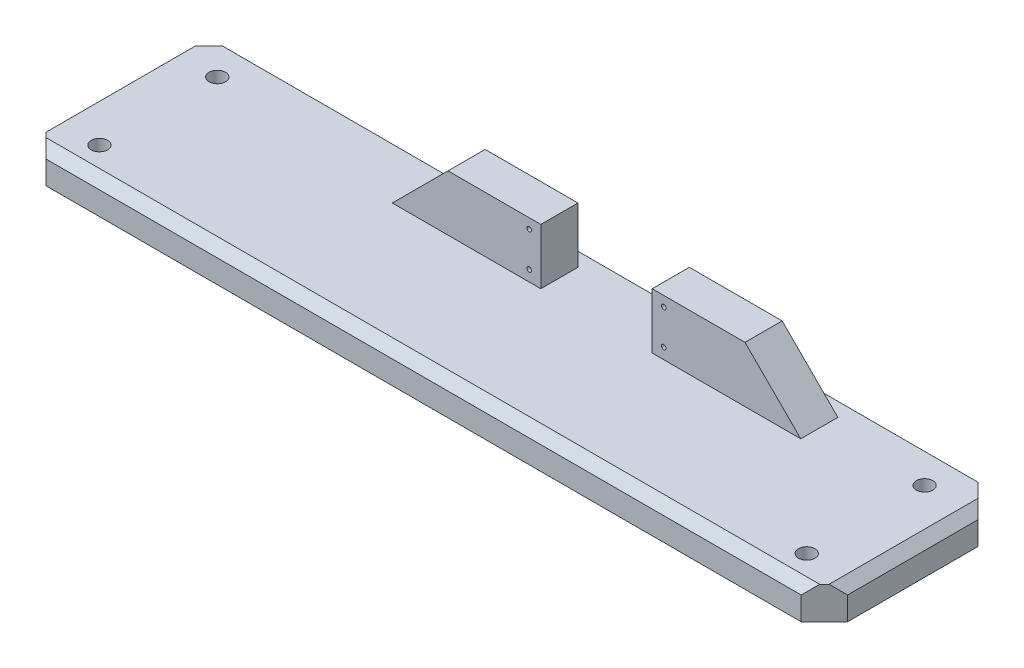
SolidWorks part; units mm, degrees
ref_plane "Front Plane" through (0, 0, 0) normal (0, 0, 1) x (1, 0, 0)
ref_plane "Top Plane" through (0, 0, 0) normal (0, 1, 0) x (1, 0, 0)
ref_plane "Right Plane" through (0, 0, 0) normal (1, 0, 0) x (0, 0, -1)
sketch "Sketch1" plane through (0, 0, 0) normal (0, 1, 0) x (1, 0, 0)
  line L1 (-79.2439, 13.0023) -> (93.4761, 13.0023)
  line L2 (-79.2439, 13.0023) -> (-79.2439, -25.0977)
  line L3 (-79.2439, -25.0977) -> (93.4761, -25.0977)
  line L4 (93.4761, 13.0023) -> (93.4761, -25.0977)
  dimension "D1" = 172.72
  dimension "D2" = 38.1
extrude "Boss-Extrude1" add sketch "Sketch1" along normal blind 7
sketch "Sketch2" plane through (0, 7, 0) normal (0, 1, 0) x (1, 0, 0)
  line L0 (93.4761, -25.0977) -> (93.4761, 13.0023) construction
  line L1 (-79.2439, -25.0977) -> (93.4761, -25.0977) construction
  circle A0 centre (-69.0839, 6.6523) radius 1.778
  circle A1 centre (-69.0839, -18.7477) radius 1.778
  circle A2 centre (83.3161, 6.6523) radius 1.778
  circle A3 centre (83.3161, -18.7477) radius 1.778
  dimension "D1" = 3.556
  dimension "D2" = 3.556
  dimension "D3" = 3.556
  dimension "D4" = 3.556
  dimension "D5" = 25.4
  dimension "D6" = 25.4
  dimension "D7" = 0
  dimension "D8" = 152.4
  dimension "D9" = 0
  dimension "D10" = 10.16
  dimension "D11" = 6.35
extrude "Cut-Extrude1" cut sketch "Sketch2" against normal blind 17
sketch "Sketch3" plane through (0, 7, 0) normal (0, 1, 0) x (1, 0, 0)
  line L0 (93.4761, 13.0023) -> (-79.2439, 13.0023) construction
  line L1 (-14.7239, 10.0023) -> (5.2761, 10.0023)
  line L2 (-14.7239, 10.0023) -> (-14.7239, 2.0023)
  line L3 (-14.7239, 2.0023) -> (5.2761, 2.0023)
  line L4 (5.2761, 10.0023) -> (5.2761, 2.0023)
  line L5 (29.2761, 10.0023) -> (49.2761, 10.0023)
  line L6 (29.2761, 10.0023) -> (29.2761, 2.0023)
  line L7 (29.2761, 2.0023) -> (49.2761, 2.0023)
  line L8 (49.2761, 10.0023) -> (49.2761, 2.0023)
  line L9 (93.4761, -25.0977) -> (93.4761, 13.0023) construction
  dimension "D1" = 20
  dimension "D2" = 20
  dimension "D3" = 8
  dimension "D4" = 8
  dimension "D5" = 3
  dimension "D6" = 3
  dimension "D7" = 24
  dimension "D8" = 44.2
extrude "Boss-Extrude2" add sketch "Sketch3" along normal blind 12
sketch "Sketch4" plane through (0, 0, -10.0023) normal (0, 0, -1) x (-1, 0, 0)
  line L0 (-49.2761, 7) -> (-29.2761, 7) construction
  line L1 (-29.2761, 19) -> (-29.2761, 7) construction
  line L2 (-5.2761, 19) -> (-5.2761, 7) construction
  circle A0 centre (-31.7761, 16.85) radius 0.5
  circle A1 centre (-31.7761, 9.35) radius 0.5
  circle A2 centre (-2.7761, 9.35) radius 0.5
  circle A3 centre (-2.7761, 16.85) radius 0.5
  dimension "D1" = 1
  dimension "D2" = 1
  dimension "D3" = 2.35
  dimension "D4" = 7.5
  dimension "D5" = 1
  dimension "D6" = 1
  dimension "D7" = 2.5
  dimension "D8" = 2.5
  dimension "D9" = 2.5
  dimension "D10" = 2.5
extrude "Cut-Extrude2" cut sketch "Sketch4" against normal blind 10
chamfer "Chamfer1" distance 12 angle 45 2 edges at (49.2761, 7, -6.0023) (-14.7239, 7, -6.0023)
chamfer "Chamfer2" distance 2 angle 45 3 edges at (93.4761, 7, 6.0477) (-79.2439, 7, 6.0477) (7.1161, 7, 25.0977)
chamfer "Chamfer3" distance 5 angle 45 4 edges at (93.4761, 2.5, -13.0023) (93.4761, 2.5, 25.0977) (-79.2439, 2.5, 25.0977) (-79.2439, 2.5, -13.0023)
